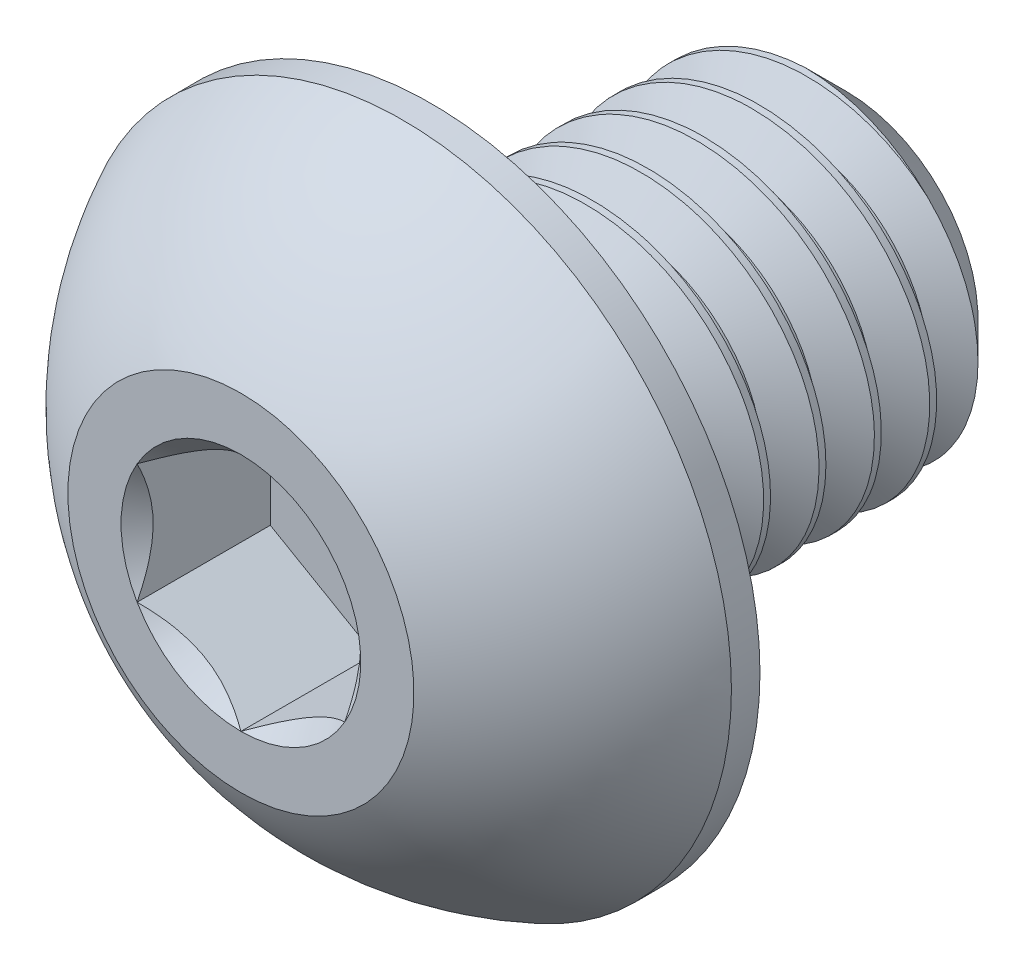
SolidWorks part; units mm, degrees
note: '?' marks a value the reader was unsure of.
ref_plane "Front" through (0, 0, 0) normal (0, 0, 1) x (1, 0, 0)
ref_plane "Top" through (0, 0, 0) normal (0, 1, 0) x (1, 0, 0)
ref_plane "Right" through (0, 0, 0) normal (1, 0, 0) x (0, 0, -1)
sketch "Sketch1" plane through (0, 0, 0) normal (1, 0, 0) x (0, 0, -1)
  line L2 (2.75, 2.5) -> (8.75, 2.5)
  line L3 (8.75, 2.5) -> (8.75, 0)
  line L4 (8.75, 0) -> (2.75, 0)
  line L6 (2.3375, 4.75) -> (2.75, 4.75) construction
  line L7 (8.75, 2.5) -> (8.75, -2.5) construction
  line L8 (0, 0) -> (2.75, 0) construction
  line L9 (2.75, 4.75) -> (2.75, -4.75) construction
  line L11 (2.75, 2.5) -> (2.75, 0)
  line L13 (0, 1.5) -> (0, -1.5) construction
  line L14 (0, 1.5) -> (0, 2.5) construction
  arc A3 (0, 2.5) -> (2.3375, 4.75) centre (4.6581, 0) cw construction
  dimension "D1" = 0.4125
revolve "Revolve1" add sketch "Sketch1" angle 360 mid plane about L4
sketch "Sketch3" plane through (0, 0, -8.75) normal (0, 0, -1) x (-1, 0, 0)
  circle A0 centre (0, 0) radius 2.5
curve "Helix/Spiral1" pitch 0.8 height 6.8 turns 8.5
chamfer "Chamfer1" distance 0.6 angle 45 1 edges at (0, 2.5, -8.75)
sketch "Sketch7" plane through (0, 0, 0) normal (1, 0, 0) x (0, 0, -1)
  line L6 (2.3375, 4.75) -> (2.75, 4.75) construction
  line L8 (0, 0) -> (2.75, 0) construction
  line L11 (2.75, 4.75) -> (2.75, -4.75) construction
  line L12 (2.3375, 4.75) -> (2.75, 4.75)
  line L13 (0, 0) -> (2.75, 0)
  line L14 (0, 1.5) -> (0, -1.5) construction
  line L15 (2.75, 4.75) -> (2.75, 0)
  line L16 (0, 2.5) -> (0, 0)
  arc A2 (2.3375, 4.75) -> (0, 2.5) centre (4.6581, 0) ccw construction
  arc A3 (2.3375, 4.75) -> (0, 2.5) centre (4.6581, 0) ccw
revolve "Revolve2" add sketch "Sketch7" angle 360 mid plane about L13
sketch "Sketch5" plane through (0, 0, 0) normal (0, 0, 1) x (1, 0, 0)
  line L1 (1.5, -0.866) -> (1.5, 0.866)
  line L2 (1.5, 0.866) -> (0, 1.7321)
  line L3 (0, 1.7321) -> (-1.5, 0.866)
  line L4 (-1.5, 0.866) -> (-1.5, -0.866)
  line L5 (-1.5, -0.866) -> (0, -1.7321)
  line L6 (0, -1.7321) -> (1.5, -0.866)
  circle A0 centre (0, 0) radius 1.5 construction
extrude "Cut-Extrude2" cut sketch "Sketch5" against normal blind 1.925
sketch "Sketch6" plane through (0, 0, 0) normal (0, 0, 1) x (1, 0, 0)
  circle A0 centre (0, 0) radius 1.7321
extrude "Cut-Extrude3" cut sketch "Sketch6" against normal blind 1.925 draft 45
sketch "Sketch2" plane through (0, 0, 0) normal (1, 0, 0) x (0, 0, -1)
  line L0 (8.15, 2.5) -> (8.85, 2.5)
  line L1 (8.85, 2.5) -> (8.55, 1.9804)
  line L2 (8.55, 1.9804) -> (8.45, 1.9804)
  line L3 (8.45, 1.9804) -> (8.15, 2.5)
  line L4 (8.3, 2.2402) -> (8.7, 2.2402) construction
  dimension "D1" = 60
  dimension "D2" = 0.1
  dimension "D3" = 0.4
sweep "Cut-Sweep1" cut profiles "Sketch2" path "Helix/Spiral1"
sketch "Sketch10" plane through (0, 0, 0) normal (1, 0, 0) x (0, 0, -1)
  line L0 (8.75, 2.5) -> (8.75, -2.5) construction
  point P0 (7.55, -2.5)
  dimension "D1" = 1.2
ref_axis "Center Axis 1" through (0, 0, -8.1113) along (0, 0, 1)?
ref_plane "Contact Plane 1" through (0, 0, -2.75) normal (0, 0, -1) x (-1, 0, 0)
ref_plane "Contact Plane 2" through (0, 0, 0) normal (0, 0, 1) x (1, 0, 0)
equation "\"D3@Helix/Spiral1\" = \"Lg@Sketch1\" + \"D4@Helix/Spiral1\""
equation "\"D2@Sketch2\" = \"D4@Helix/Spiral1\" * .125"
equation "\"D3@Sketch2\" = \"D4@Helix/Spiral1\" * .5"
equation "\"D1@Chamfer1\" = \"D4@Helix/Spiral1\" * .75"
equation "\"D1@Cut-Extrude2\" = \"Head Ht@Sketch1\" * .7"
equation "\"D1@Sketch1\" = \"Head Ht@Sketch1\" * .15"
equation "\"D1@Sketch10\" = \"D4@Helix/Spiral1\" * 1.5"
equation "\"D1@Cut-Extrude3\" = \"D1@Cut-Extrude2\""
